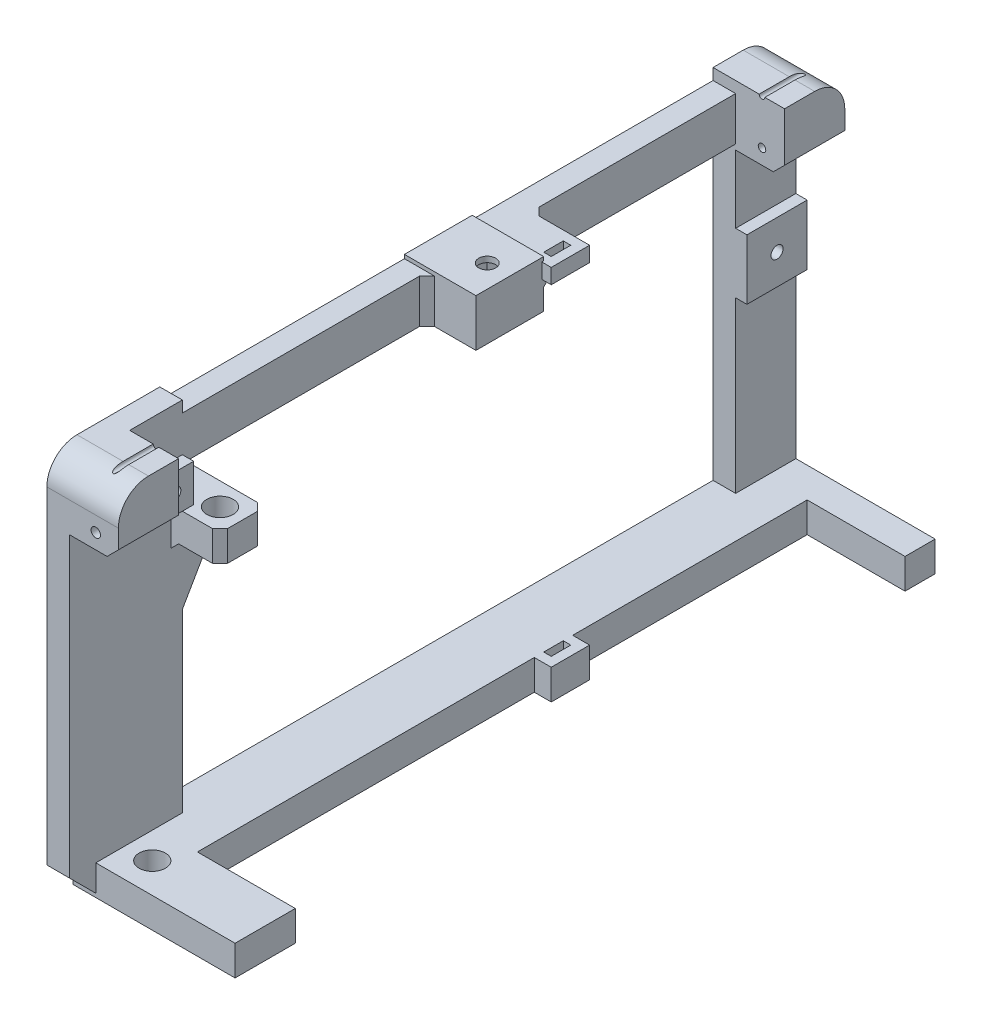
SolidWorks part; units mm, degrees
ref_plane "Front Plane" through (0, 0, 0) normal (0, 0, 1) x (1, 0, 0)
ref_plane "Top Plane" through (0, 0, 0) normal (0, 1, 0) x (1, 0, 0)
ref_plane "Right Plane" through (0, 0, 0) normal (1, 0, 0) x (0, 0, -1)
sketch "Sketch1" plane through (0, 0, 0) normal (1, 0, 0) x (0, 0, -1)
  line L0 (0, 0) -> (-8, 0)
  line L1 (-8, 0) -> (-8, -8)
  line L2 (-8, -8) -> (178, -8)
  line L3 (178, -8) -> (178, 0)
  line L4 (178, 0) -> (170, 0)
  line L5 (170, 0) -> (0, 0)
  point P8 (0, 0)
  dimension "D1" = 170
  dimension "D2" = 8
extrude "Boss-Extrude1" add sketch "Sketch1" along normal blind 4
sketch "Sketch2" plane through (4, 0, 0) normal (1, 0, 0) x (0, 0, -1)
  line L0 (178, 0) -> (-8, 0) construction
  line L1 (-8, -8) -> (0, -8)
  line L2 (-8, -8) -> (-8, 0)
  line L3 (-8, 0) -> (0, 0)
  line L5 (-8, -8) -> (178, -8) construction
  line L6 (178, 0) -> (170, 0)
  line L7 (178, 0) -> (178, -8)
  line L8 (178, -8) -> (170, -8)
  line L9 (170, 0) -> (170, -8)
  line L10 (0, -8) -> (8, -8)
  line L11 (8, -8) -> (8, 0)
  line L12 (8, 0) -> (0, 0)
extrude "Boss-Extrude2" add sketch "Sketch2" along normal blind 26
extrude "Boss-Extrude3" add sketch "Sketch1<2>" against normal blind 7
sketch "Sketch1<2>" plane through (0, 0, 0) normal (1, 0, 0) x (0, 0, -1) same geometry as "Sketch1"
sketch "Sketch4" plane through (-7, 0, 0) normal (-1, 0, 0) x (0, 0, 1)
  line L0 (-178, 0) -> (-178, 87)
  line L2 (-162, 95) -> (-162, 92)
  line L3 (-170, 0) -> (0, 0) construction
  line L4 (-170, 95) -> (-170, 53) construction
  line L5 (-170, 53) -> (-170, 0) construction
  line L6 (-170, 95) -> (-178, 95) construction
  line L7 (15, 2.4) -> (0, 2.4) construction
  line L8 (8, -8) -> (-178, -8)
  line L9 (8, -8) -> (8, 0)
  line L11 (-178, -8) -> (-178, 0)
  line L12 (15, 2.4) -> (15, 77.4)
  line L13 (15, 77.4) -> (0, 77.4) construction
  line L15 (-15, 2.4) -> (-15, 0)
  line L18 (8, 0) -> (15, 0)
  line L19 (15, 0) -> (15, 2.4)
  line L21 (0, 2.4) -> (0, 77.4) construction
  line L22 (-15, 2.4) -> (0, 2.4) construction
  line L23 (-15, 2.4) -> (-15, 77.4)
  line L24 (-15, 0) -> (-162, 0)
  line L26 (2.4, 95) -> (-15, 95)
  line L27 (-15, 95) -> (-15, 92)
  line L28 (0, 77.4) -> (-10, 77.4) construction
  line L29 (-10, 77.4) -> (-15, 77.4) construction
  line L30 (-170, 95) -> (-162, 95)
  line L31 (-15, 95) -> (-162, 95) construction
  line L32 (-178, 95) -> (-178, 87) construction
  line L33 (15, 77.4) -> (15, 87)
  line L34 (2.4, 95) -> (7, 95)
  line L35 (-15, 80.4) -> (-162, 80.4)
  line L36 (-15, 92) -> (-162, 92)
  line L37 (-15, 80.4) -> (-15, 77.4)
  line L38 (-162, 80.4) -> (-162, 0)
  arc A1 (-170, 95) -> (-178, 87) centre (-170, 87) ccw
  arc A2 (15, 87) -> (7, 95) centre (7, 87) ccw
  point P8 (-170, 53)
  point P9 (-10, 77.4)
  dimension "D8" = 8
  dimension "D1" = 53
  dimension "D2" = 15
  dimension "D3" = 15
  dimension "D4" = 75
  dimension "D5" = 10
  dimension "D6" = 95
  dimension "D7" = 8
  dimension "D9" = 3
extrude "Boss-Extrude4" add sketch "Sketch4" along normal blind 6
sketch "Sketch10" plane through (-7, 0, 0) normal (1, 0, 0) x (0, 0, -1)
  line L0 (15, 82.4) -> (5, 82.4)
  line L1 (15, 95) -> (15, 92) construction
  line L2 (5, 82.4) -> (5, 72.4)
  line L3 (5, 72.4) -> (10, 72.4)
  line L4 (10, 72.4) -> (10, 77.4) construction
  line L5 (10, 77.4) -> (15, 77.4) construction
  line L6 (10, 77.4) -> (15, 77.4) construction
  line L7 (15, 77.4) -> (15, 82.4)
  line L8 (10, 72.4) -> (15, 72.4)
  line L9 (15, 2.4) -> (15, 77.4) construction
  line L10 (15, 72.4) -> (15, 77.4)
  line L11 (170, 61) -> (178, 61)
  line L12 (178, 61) -> (178, 53)
  line L13 (178, 0) -> (178, 87) construction
  line L14 (178, 53) -> (170, 53) construction
  line L15 (162, 95) -> (162, 92) construction
  line L16 (170, 53) -> (170, 61) construction
  line L17 (162, 61) -> (162, 45)
  line L19 (162, 45) -> (178, 45)
  line L20 (178, 45) -> (178, 53)
  line L21 (170, 61) -> (162, 61)
extrude "Boss-Extrude6" add sketch "Sketch10" along normal blind 3 contours L3 L8 L10 L7 L0 L2
extrude "Boss-Extrude7" add sketch "Sketch10<3>" along normal blind 3 contours L11 L21 L17 L19 L20 L12 region at (-7, 53, -170)
sketch "Sketch10<3>" plane through (-7, 0, 0) normal (1, 0, 0) x (0, 0, -1) same geometry as "Sketch10"
hole_wizard "Ø7.0mm Dowel Hole1" positions "3DSketch2" profile "Sketch5" hole size "Ø7.0" standard "ANSI Metric" end condition through all
sketch3d "3DSketch2"
  point P0 (0, 0, 0)
  point P3 (0, 0, 0)
  point P5 (0, 0, 0)
  point P7 (0, 0, 0)
  point P9 (0, 0, 0)
sketch "Sketch5" plane through (0, 0, 0) normal (1, 0, 0) x (0, 0, 1)
  line L0 (0, 0) -> (0, 8)
  line L1 (0, 8) -> (3.5, 8)
  line L2 (3.5, 8) -> (3.5, 0)
  line L5 (3.5, 0) -> (0, 0)
  line L11 (0, -6.35) -> (0, 107.95) construction
  dimension "Thru Hole Dia." = 7
  dimension "Thru Hole Depth" = 8
hole_wizard "M3 Clearance Hole2" positions "3DSketch3" profile "Sketch6" hole size "M3" standard "ANSI Metric" end condition through all
sketch3d "3DSketch3"
  point P0 (-7, 53, -170)
sketch "Sketch6" plane through (-7, 53, -170) normal (0, 1, 0) x (0, 0, -1)
  line L0 (0, 0) -> (0, 6)
  line L1 (0, 6) -> (1.6, 6)
  line L2 (1.6, 6) -> (1.6, 0)
  line L5 (1.6, 0) -> (0, 0)
  line L11 (0, -6.35) -> (0, 107.95) construction
  dimension "Thru Hole Dia." = 3.2
  dimension "Thru Hole Depth" = 6
hole_wizard "M3 Clearance Hole3" positions "3DSketch4" profile "Sketch9" hole size "M3" standard "ANSI Metric" end condition through all
sketch3d "3DSketch4"
  point P0 (-7, 77.4, -10)
  point P3 (-7, 77.4, -10)
  point P5 (-7, 77.4, -10)
  point P7 (-7, 77.4, -10)
sketch "Sketch9" plane through (-7, 77.4, -10) normal (0, 1, 0) x (0, 0, 1)
  line L0 (0, 0) -> (0, 37)
  line L1 (0, 37) -> (1.6, 37)
  line L2 (1.6, 37) -> (1.6, 0)
  line L5 (1.6, 0) -> (0, 0)
  line L11 (0, -6.35) -> (0, 107.95) construction
  dimension "Thru Hole Dia." = 3.2
  dimension "Thru Hole Depth" = 37
hole_wizard "M3 Clearance Hole4" positions "Sketch11" profile "Sketch12" hole size "M3" standard "ANSI Metric" end condition through all
sketch "Sketch11" plane through (0, 0, 0) normal (1, 0, 0) x (0, 0, -1)
  point P0 (10, 77.4)
  point P3 (170, 53)
sketch "Sketch12" plane through (0, 77.4, -10) normal (0, 1, 0) x (0, 0, -1)
  line L0 (0, 0) -> (0, 13)
  line L1 (0, 13) -> (1.6, 13)
  line L2 (1.6, 13) -> (1.6, 0)
  line L5 (1.6, 0) -> (0, 0)
  line L11 (0, -6.35) -> (0, 107.95) construction
  dimension "Thru Hole Dia." = 3.2
  dimension "Thru Hole Depth" = 13
sketch "Sketch13" plane through (0, 0, 0) normal (0, 1, 0) x (1, 0, 0)
  line L0 (0, 0) -> (5, 0) construction
  line L1 (5, 0) -> (5, 102.6) construction
  line L2 (6, 107.7) -> (8.5, 107.7)
  line L3 (4, 170) -> (4, 8) construction
  line L4 (6, 105.2) -> (6, 100)
  line L6 (6, 100) -> (4, 100)
  line L8 (4, 105.2) -> (6, 105.2)
  line L10 (4, 107.7) -> (6, 107.7)
  line L12 (6, 97.5) -> (4, 97.5)
  line L14 (8.5, 107.7) -> (8.5, 97.5)
  line L15 (5, 105.2) -> (5, 107.7) construction
  line L16 (4, 105.2) -> (4, 107.7)
  line L17 (4, 100) -> (4, 97.5)
  line L18 (8.5, 97.5) -> (6, 97.5)
  line L19 (6, 102.6) -> (5, 102.6) construction
  point P13 (5, 100)
  point P21 (5, 107.7)
  dimension "D1" = 100
  dimension "D2" = 5
  dimension "D3" = 5.2
  dimension "D4" = 2.5
extrude "Boss-Extrude8" add sketch "Sketch13" against normal up to vertex (8 mm away) up to point (4, -8, -170)
sketch "Sketch14" plane through (-7, 0, 0) normal (1, 0, 0) x (0, 0, -1)
  line L0 (15, 72.4) -> (24, 72.4)
  line L1 (24, 72.4) -> (24, 62.4)
  line L2 (24, 62.4) -> (15, 46.8115)
  line L3 (15, 2.4) -> (15, 77.4) construction
  line L4 (15, 46.8115) -> (15, 72.4)
  line L5 (18, 72.4) -> (18, 52.0077) construction
  dimension "D1" = 30
  dimension "D2" = 8
  dimension "D3" = 6
  dimension "D4" = 10
extrude "Boss-Extrude9" add sketch "Sketch14" against normal up to vertex (6 mm away) up to point (-13, 0, -15)
sketch "Sketch15" plane through (-7, 0, 0) normal (1, 0, 0) x (0, 0, -1)
  line L1 (24, 72.4) -> (12, 72.4)
  line L2 (24, 72.4) -> (24, 64.4)
  line L3 (24, 64.4) -> (12, 64.4)
  line L4 (12, 72.4) -> (12, 64.4)
  point P5 (18, 72.4)
  dimension "D1" = 8
extrude "Boss-Extrude10" add sketch "Sketch15" along normal blind 13
chamfer "Chamfer1" distance 2 angle 45 1 edges at (-7, 64.4, -18)
sketch "Sketch16" plane through (0, 72.4, 0) normal (0, 1, 0) x (1, 0, 0)
  line L0 (0, 0) -> (0, 10) construction
  line L1 (0, -8) -> (0, 178) construction
  line L2 (0, 10) -> (0, 18) construction
  line L3 (-7, 10) -> (0, 10) construction
  line L4 (-7, 18) -> (0, 18) construction
  line L5 (-7, 15) -> (-7, 24) construction
  circle A0 centre (0, 18) radius 3.5
  dimension "D1" = 7
extrude "Cut-Extrude1" cut sketch "Sketch16" against normal up to next
chamfer "Chamfer2" distance 2 angle 45 2 edges at (6, 68.4, -24) (6, 68.4, -12)
sketch "Sketch17" plane through (-7, 0, 0) normal (1, 0, 0) x (0, 0, -1)
  line L0 (1, 95) -> (1, 79)
  line L1 (-2.4, 95) -> (15, 95) construction
  line L2 (1, 79) -> (-15, 79)
  line L3 (-15, 2.4) -> (-15, 77.4) construction
  line L4 (-15, 79) -> (-15, 87)
  line L5 (-7, 95) -> (1, 95)
  line L6 (170, 95) -> (162, 95)
  line L7 (162, 95) -> (162, 79)
  line L8 (162, 79) -> (178, 79)
  line L9 (178, 79) -> (178, 87)
  line L10 (178, 0) -> (178, 87) construction
  arc A0 (-15, 87) -> (-7, 95) centre (-7, 87) cw
  arc A1 (178, 87) -> (170, 95) centre (170, 87) ccw
  arc A2 (-7, 95) -> (-15, 87) centre (-7, 87) ccw construction
  dimension "D1" = 8
  dimension "D2" = 8
extrude "Boss-Extrude11" add sketch "Sketch17" along normal blind 13
sketch "Sketch18" plane through (0, 0, 15) normal (0, 0, 1) x (1, 0, 0)
  line L0 (0, 0) -> (0, 79) construction
  line L1 (6, 79) -> (-7, 79) construction
  line L2 (0, 79) -> (0, 87) construction
  line L3 (-13, 87) -> (6, 87) construction
  line L4 (0, 87) -> (0, 95) construction
  line L5 (-13, 95) -> (6, 95) construction
  circle A0 centre (0, 95) radius 0.75
  point P5 (0, 83)
  dimension "D1" = 1.5
extrude "Cut-Extrude2" cut sketch "Sketch18" against normal through all both and the other way through all
hole_wizard "Tap Drill for M3x0.5 Tap1" positions "3DSketch5" profile "Sketch20" hole size "M3x0.5" standard "ANSI Metric" end condition up to next
sketch3d "3DSketch5"
  point P0 (0, 83, 15)
sketch "Sketch20" plane through (0, 83, 15) normal (1, 0, 0) x (0, -1, 0)
  line L0 (0, 0) -> (0, 16)
  line L1 (0, 16) -> (1.25, 16)
  line L2 (1.25, 16) -> (1.25, 0)
  line L5 (1.25, 0) -> (0, 0)
  line L11 (0, -6.35) -> (0, 107.95) construction
  dimension "Thru Hole Dia." = 2.5
  dimension "Thru Hole Depth" = 16
sketch "Sketch22" plane through (0, 0, -178) normal (0, 0, -1) x (-1, 0, 0)
  line L0 (0, 79) -> (0, 87) construction
  point P0 (0, 83)
hole_wizard "Ø2.0mm Dowel Hole4" positions "3DSketch7" profile "Sketch23" hole size "Ø2.0" standard "ANSI Metric" end condition up to next
sketch3d "3DSketch7"
  point P0 (0, 83, 15)
sketch "Sketch23" plane through (0, 83, 15) normal (1, 0, 0) x (0, -1, 0)
  line L0 (0, 0) -> (0, 193)
  line L1 (0, 193) -> (1, 193)
  line L2 (1, 193) -> (1, 0)
  line L5 (1, 0) -> (0, 0)
  line L11 (0, -6.35) -> (0, 107.95) construction
  dimension "Thru Hole Dia." = 2
  dimension "Thru Hole Depth" = 193
chamfer "Chamfer3" distance 3 angle 45 2 edges at (6, 79, -170) (6, 79, 7)
sketch "Sketch24" plane through (0, 0, 0) normal (1, 0, 0) x (0, 0, -1)
  line L0 (89, 103.1751) -> (89, 65.5188) construction
  line L1 (80, 93) -> (98, 93)
  line L2 (80, 93) -> (80, 80.4)
  line L3 (80, 80.4) -> (98, 80.4)
  line L4 (98, 93) -> (98, 80.4)
  line L5 (15, 80.4) -> (162, 80.4) construction
  line L6 (0, 2.4) -> (0, 77.4) construction
  line L7 (15, 95) -> (162, 95) construction
  point P12 (89, 93)
  dimension "D1" = 80
  dimension "D2" = 2
  dimension "D3" = 18
extrude "Boss-Extrude12" add sketch "Sketch24" along normal blind 6 and the other way up to vertex other way up to point (-13, 92, -15)
sketch "Sketch25" plane through (0, 0, 0) normal (1, 0, 0) x (0, 0, -1)
  line L0 (15, 80.4) -> (162, 80.4) construction
  line L1 (82, 80.4) -> (96, 80.4)
  line L2 (82, 80.4) -> (82, 91.5)
  line L3 (82, 91.5) -> (96, 91.5)
  line L4 (96, 80.4) -> (96, 91.5)
  line L5 (80, 93) -> (80, 80.4) construction
  line L6 (89, 103.1751) -> (89, 65.5188) construction
  line L7 (80, 93) -> (98, 93) construction
  point P8 (89, 91.5)
  dimension "D1" = 2
  dimension "D2" = 1.5
extrude "Cut-Extrude3" cut sketch "Sketch25" against normal mid plane 10
chamfer "Chamfer4" distance 2 angle 45 6 edges at (-7, 86.2, -80) (-5, 85.95, -96) (-7, 86.2, -98) (-5, 85.95, -82) (5, 85.95, -96) (5, 85.95, -82)
sketch "Sketch26" plane through (0, 0, 0) normal (1, 0, 0) x (0, 0, -1)
  line L0 (80, 93) -> (98, 93) construction
  line L1 (89, 93) -> (86.75, 93)
  line L2 (89, 93) -> (89, 91.5)
  line L3 (89, 91.5) -> (86.75, 91.5)
  line L4 (86.75, 93) -> (86.75, 91.5)
  line L5 (82, 91.5) -> (96, 91.5) construction
  line L7 (89, 65.5188) -> (89, 103.1751) construction
  dimension "D1" = 4.5
revolve "Cut-Revolve1" cut sketch "Sketch26" angle 360 about L7
sketch "Sketch27" plane through (0, 92, 0) normal (0, 1, 0) x (1, 0, 0)
  line L0 (8.5, 107.7) -> (-7, 107.7)
  line L1 (-7, 100) -> (-7, 162) construction
  line L2 (8.5, 107.7) -> (8.5, 97.5)
  line L3 (8.5, 97.5) -> (-7, 97.5)
  line L4 (-7, 97.5) -> (-7, 107.7)
  line L5 (4, 105.2) -> (6, 105.2)
  line L6 (6, 105.2) -> (6, 100)
  line L7 (6, 100) -> (4, 100)
  line L8 (4, 100) -> (4, 105.2)
extrude "Boss-Extrude13" add sketch "Sketch27" against normal blind 4
chamfer "Chamfer5" distance 2 angle 45 4 edges at (-7, 90, -107.7) (-7, 88, -103.85) (-6, 88, -99) (0.5, 88, -98)
chamfer "Chamfer6" distance 7 angle 45 1 edges at (-10, 0, 8)
